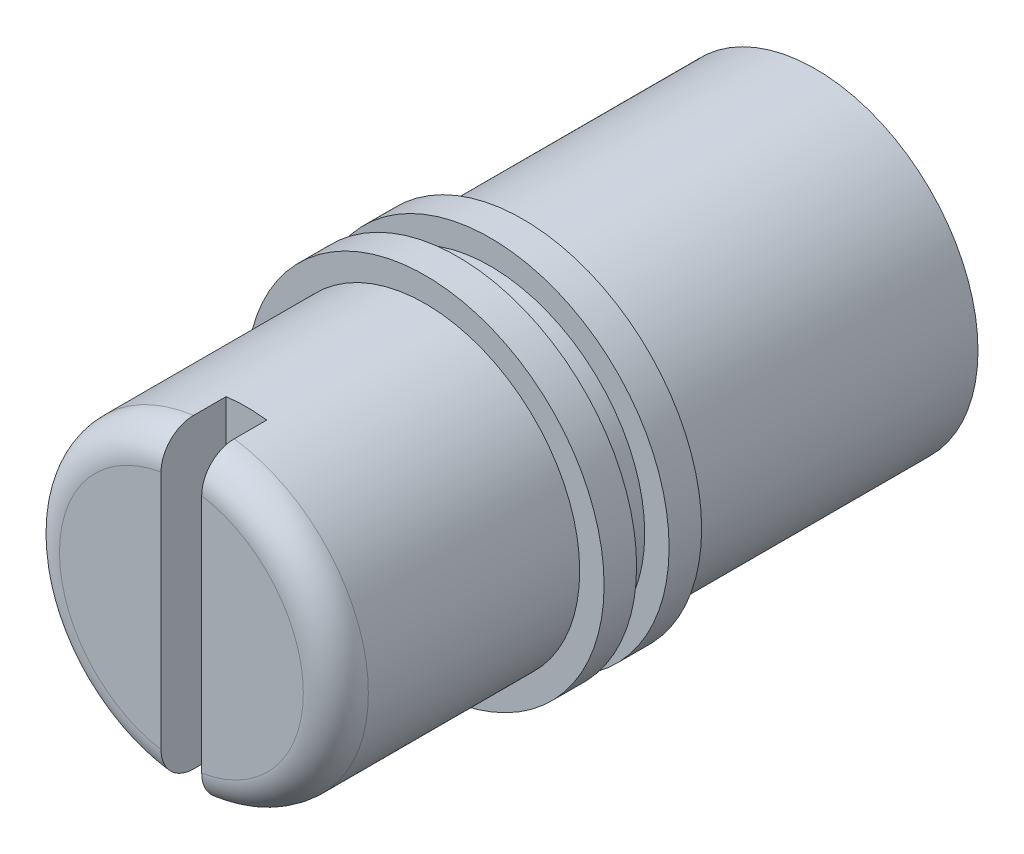
SolidWorks part; units mm, degrees
material "Alloy Steel"
ref_plane "Front Plane" through (0, 0, 0) normal (0, 0, 1) x (1, 0, 0)
ref_plane "Top Plane" through (0, 0, 0) normal (0, 1, 0) x (1, 0, 0)
ref_plane "Right Plane" through (0, 0, 0) normal (1, 0, 0) x (0, 0, -1)
sketch "Sketch1" plane through (0, 0, 0) normal (0, 0, 1) x (1, 0, 0)
  circle A0 centre (0, 0) radius 10
  circle A1 centre (0, 0) radius 11
  circle A2 centre (0, 0) radius 9.5
  dimension "D1" = 20
  dimension "D2" = 22
  dimension "D3" = 19
extrude "Boss-Extrude1" add sketch "Sketch1" along normal blind 19 contours A2 region at (0, 0, 0)
extrude "Boss-Extrude4" add sketch "Sketch1<5>" against normal blind 20 contours A0
sketch "Sketch1<5>" plane through (0, 0, 0) normal (0, 0, 1) x (1, 0, 0) same geometry as "Sketch1"
extrude "Boss-Extrude2" add sketch "Sketch1<3>" along normal blind 2 from offset 2 contours A1 A0 | A0 A2 region at (-9.7172, 0, 0) region at (-10.6889, 0, 0)
sketch "Sketch1<3>" plane through (0, 0, 0) normal (0, 0, 1) x (1, 0, 0) same geometry as "Sketch1"
extrude "Boss-Extrude3" add sketch "Sketch1<4>" against normal blind 2 contours A1 A0 region at (-10.6889, 0, 0)
sketch "Sketch1<4>" plane through (0, 0, 0) normal (0, 0, 1) x (1, 0, 0) same geometry as "Sketch1"
fillet "Fillet1" radius 2 1 edges at (9.5, 0, 19)
sketch "Sketch4" plane through (0, 0, 19) normal (0, 0, 1) x (1, 0, 0)
  line L2 (-1.25, -9.4174) -> (-1.25, 9.4174)
  line L4 (1.25, -9.4174) -> (1.25, 9.4174)
  line L5 (-1.25, -9.4174) -> (1.25, 9.4174) construction
  line L6 (-1.25, 9.4174) -> (1.25, -9.4174) construction
  circle A0 centre (0, 0) radius 9.5 construction
  arc A1 (1.25, 9.4174) -> (-1.25, 9.4174) centre (0, 0) ccw
  arc A2 (-1.25, -9.4174) -> (1.25, -9.4174) centre (0, 0) ccw
  point P0 (0, 0)
  dimension "D1" = 2.5
extrude "Cut-Extrude3" cut sketch "Sketch4" against normal blind 4
sketch "Sketch6" plane through (0, 0, -20) normal (0, 0, -1) x (-1, 0, 0)
  circle A0 centre (0, 0) radius 5
  dimension "D1" = 10
extrude "Cut-Extrude4" cut sketch "Sketch6" against normal blind 25
